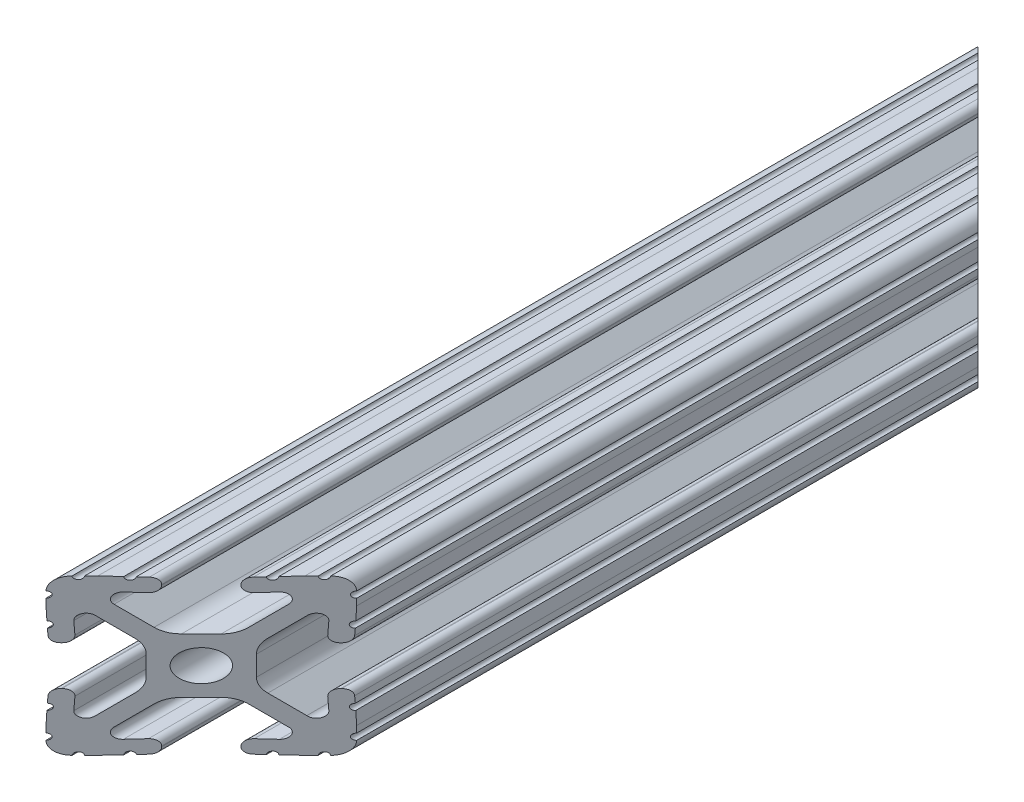
SolidWorks part; units mm, degrees
ref_plane "Front" through (0, 0, 0) normal (0, 0, 1) x (1, 0, 0)
ref_plane "Top" through (0, 0, 0) normal (0, 1, 0) x (1, 0, 0)
ref_plane "Right" through (0, 0, 0) normal (1, 0, 0) x (0, 0, -1)
ref_plane "Bottom" through (0, 25.4, 0) normal (0, 1, 0) x (-1, 0, 0)
ref_plane "Left" through (25.4, 0, 0) normal (1, 0, 0) x (0, 0, -1)
sketch "Sketch1" plane through (0, 0, 0) normal (0, 0, 1) x (1, 0, 0)
  line L0 (25.4334, 2.1492) -> (25.4334, 2.1323)
  line L1 (23.3169, 0.0156) -> (23.3, 0.0156)
  line L2 (22.284, 0.0156) -> (21.2003, 0.0156)
  line L3 (21.2003, 0.0156) -> (19.0664, 0.0901)
  line L4 (6.4007, 0.0901) -> (4.2668, 0.0156)
  line L5 (4.2668, 0.0156) -> (3.1831, 0.0156)
  line L6 (2.1671, 0.0156) -> (2.1502, 0.0156)
  line L7 (0.0335, 2.1323) -> (0.0335, 2.1492)
  line L8 (0.0335, 3.1652) -> (0.0335, 4.249)
  line L9 (0.0335, 4.249) -> (0.1081, 6.3829)
  line L10 (0.108, 19.0484) -> (0.0335, 21.1824)
  line L11 (0.0335, 21.1824) -> (0.0335, 22.2661)
  line L12 (0.0335, 23.2821) -> (0.0335, 23.299)
  line L13 (2.1501, 25.4157) -> (2.1671, 25.4156)
  line L14 (3.1831, 25.4156) -> (4.2668, 25.4156)
  line L15 (4.2668, 25.4156) -> (6.4007, 25.3411)
  line L16 (19.0663, 25.3411) -> (21.2003, 25.4156)
  line L17 (21.2003, 25.4156) -> (22.284, 25.4156)
  line L18 (23.2999, 25.4156) -> (23.3169, 25.4156)
  line L19 (25.4336, 23.299) -> (25.4336, 23.2821)
  line L20 (25.4336, 22.2661) -> (25.4336, 21.1824)
  line L21 (25.4336, 21.1824) -> (25.3591, 19.0485)
  line L22 (25.3589, 6.3829) -> (25.4334, 4.249)
  line L23 (25.4334, 4.249) -> (25.4334, 3.1652)
  line L24 (12.7336, 17.2115) -> (11.1094, 17.2115)
  line L25 (7.6974, 19.3084) -> (8.8644, 18.1414)
  line L26 (8.2292, 12.7156) -> (8.2292, 14.3482)
  line L27 (12.7336, 17.2115) -> (14.3575, 17.2115)
  line L28 (17.2378, 12.7156) -> (17.2378, 14.3484)
  line L29 (17.2378, 12.7156) -> (17.2378, 11.0831)
  line L30 (8.2292, 12.7156) -> (8.2292, 11.0831)
  line L31 (16.6026, 18.1414) -> (19.7969, 21.3357)
  line L32 (18.1678, 8.8381) -> (21.3535, 5.6523)
  line L33 (5.6701, 4.0957) -> (8.8643, 7.2899)
  line L34 (12.7336, 8.2198) -> (11.1094, 8.2198)
  line L35 (12.7336, 8.2198) -> (14.3574, 8.2198)
  line L36 (19.7967, 4.0956) -> (16.6025, 7.2899)
  line L37 (7.2993, 16.5932) -> (4.0415, 19.8511)
  line L38 (7.2993, 8.838) -> (4.0415, 5.5802)
  line L39 (7.6974, 19.3084) -> (5.5981, 21.4076)
  line L40 (7.4161, 25.3057) -> (8.4818, 25.25)
  line L41 (8.4086, 23.0512) -> (6.352, 23.1414)
  line L42 (9.4951, 24.1004) -> (9.4951, 24.2008)
  line L43 (0.1992, 16.9673) -> (0.1435, 18.0331)
  line L44 (1.3488, 15.9541) -> (1.2484, 15.9541)
  line L45 (2.398, 17.0406) -> (2.3077, 19.0972)
  line L46 (0.1435, 7.3983) -> (0.1992, 8.464)
  line L47 (1.2484, 9.4772) -> (1.3488, 9.4773)
  line L48 (2.398, 8.3907) -> (2.3077, 6.3341)
  line L49 (8.4819, 0.1813) -> (7.4161, 0.1256)
  line L50 (9.4951, 1.3309) -> (9.4951, 1.2305)
  line L51 (8.4086, 2.3801) -> (6.352, 2.2898)
  line L52 (18.0509, 0.1256) -> (16.9852, 0.1813)
  line L53 (17.0585, 2.3801) -> (19.1151, 2.2898)
  line L54 (25.2677, 8.464) -> (25.3235, 7.3983)
  line L55 (24.1183, 9.4772) -> (24.2187, 9.4773)
  line L56 (23.0691, 8.3907) -> (23.1594, 6.3341)
  line L57 (25.3235, 18.0331) -> (25.2678, 16.9674)
  line L58 (23.069, 17.0407) -> (23.1593, 19.0973)
  line L59 (16.984, 25.25) -> (18.0509, 25.3057)
  line L60 (15.9709, 24.1004) -> (15.9709, 24.2008)
  line L61 (17.0573, 23.0512) -> (19.1151, 23.1414)
  line L62 (15.972, 1.3309) -> (15.972, 1.2305)
  line L63 (18.1678, 16.5934) -> (21.4254, 19.8511)
  arc A0 (25.4334, 3.1652) -> (25.4334, 2.1492) centre (25.4334, 2.6572) ccw
  arc A1 (23.3169, 0.0156) -> (25.4334, 2.1323) centre (23.3168, 2.1323) ccw
  arc A2 (23.3, 0.0156) -> (22.284, 0.0156) centre (22.792, 0.0105) ccw
  arc A3 (19.0664, 0.0901) -> (18.0509, 0.1256) centre (18.5588, 0.1118) ccw
  arc A4 (7.4161, 0.1256) -> (6.4007, 0.0901) centre (6.9084, 0.1079) ccw
  arc A5 (3.1831, 0.0156) -> (2.1671, 0.0156) centre (2.6751, 0.012) ccw
  arc A6 (0.0335, 2.1323) -> (2.1502, 0.0156) centre (2.1502, 2.1323) ccw
  arc A7 (0.0335, 2.1492) -> (0.0335, 3.1652) centre (0.0335, 2.6572) ccw
  arc A8 (0.1081, 6.3829) -> (0.1435, 7.3983) centre (0.1291, 6.8905) ccw
  arc A9 (0.1435, 18.0331) -> (0.108, 19.0484) centre (0.1258, 18.5408) ccw
  arc A10 (0.0335, 22.2661) -> (0.0335, 23.2821) centre (0.0371, 22.7741) ccw
  arc A11 (2.1501, 25.4157) -> (0.0335, 23.299) centre (2.1502, 23.299) ccw
  arc A12 (2.1671, 25.4156) -> (3.1831, 25.4156) centre (2.6751, 25.412) ccw
  arc A13 (6.4007, 25.3411) -> (7.4161, 25.3057) centre (6.9085, 25.3266) ccw
  arc A14 (18.0509, 25.3057) -> (19.0663, 25.3411) centre (18.5586, 25.3234) ccw
  arc A15 (22.284, 25.4156) -> (23.2999, 25.4156) centre (22.792, 25.412) ccw
  arc A16 (25.4336, 23.299) -> (23.3169, 25.4156) centre (23.3169, 23.299) ccw
  arc A17 (25.4336, 23.2821) -> (25.4336, 22.2661) centre (25.4336, 22.7741) ccw
  arc A18 (25.3591, 19.0485) -> (25.3235, 18.0331) centre (25.3338, 18.5411) ccw
  arc A19 (25.3235, 7.3983) -> (25.3589, 6.3829) centre (25.3412, 6.8906) ccw
  circle A20 centre (12.7336, 12.7156) radius 2.5527
  arc A21 (8.8644, 18.1414) -> (11.1094, 17.2115) centre (11.1094, 20.3865) ccw
  arc A22 (8.2292, 14.3482) -> (7.2993, 16.5932) centre (5.0542, 14.3482) ccw
  arc A23 (14.3575, 17.2115) -> (16.6026, 18.1414) centre (14.3575, 20.3865) ccw
  arc A24 (18.1678, 16.5934) -> (17.2378, 14.3484) centre (20.4128, 14.3484) ccw
  arc A25 (17.2378, 11.0831) -> (18.1678, 8.8381) centre (20.4128, 11.0831) ccw
  arc A26 (7.2993, 8.838) -> (8.2292, 11.0831) centre (5.0542, 11.0831) ccw
  arc A27 (11.1094, 8.2198) -> (8.8643, 7.2899) centre (11.1094, 5.0448) ccw
  arc A28 (16.6025, 7.2899) -> (14.3574, 8.2198) centre (14.3574, 5.0448) ccw
  arc A29 (4.0415, 19.8511) -> (2.3077, 19.0972) centre (3.3231, 19.1327) ccw
  arc A30 (2.3077, 6.3341) -> (4.0415, 5.5802) centre (3.3231, 6.2986) ccw
  arc A31 (5.6701, 4.0957) -> (6.352, 2.2898) centre (6.308, 3.3049) ccw
  arc A32 (19.1151, 2.2898) -> (19.7967, 4.0956) centre (19.1587, 3.3049) ccw
  arc A33 (21.3535, 5.6523) -> (23.1594, 6.3341) centre (22.1443, 6.2902) ccw
  arc A34 (23.1593, 19.0973) -> (21.4254, 19.8511) centre (22.1439, 19.1327) ccw
  arc A35 (19.7969, 21.3357) -> (19.1151, 23.1414) centre (19.1588, 22.1264) ccw
  arc A36 (6.352, 23.1414) -> (5.5981, 21.4076) centre (6.3165, 22.1261) ccw
  arc A37 (9.4951, 24.2008) -> (8.4818, 25.25) centre (8.4452, 24.2008) ccw
  arc A38 (8.4086, 23.0512) -> (9.4951, 24.1004) centre (8.4452, 24.1004) ccw
  arc A39 (0.1992, 16.9673) -> (1.2484, 15.9541) centre (1.2484, 17.004) ccw
  arc A40 (1.3488, 15.9541) -> (2.398, 17.0406) centre (1.3488, 17.004) ccw
  arc A41 (1.2484, 9.4772) -> (0.1992, 8.464) centre (1.2484, 8.4273) ccw
  arc A42 (2.398, 8.3907) -> (1.3488, 9.4773) centre (1.3488, 8.4274) ccw
  arc A43 (8.4819, 0.1813) -> (9.4951, 1.2305) centre (8.4452, 1.2305) ccw
  arc A44 (9.4951, 1.3309) -> (8.4086, 2.3801) centre (8.4452, 1.3309) ccw
  arc A45 (15.972, 1.2305) -> (16.9852, 0.1813) centre (17.0219, 1.2305) ccw
  arc A46 (17.0585, 2.3801) -> (15.972, 1.3309) centre (17.0219, 1.3309) ccw
  arc A47 (25.2677, 8.464) -> (24.2187, 9.4773) centre (24.2185, 8.4274) ccw
  arc A48 (24.1183, 9.4772) -> (23.0691, 8.3907) centre (24.1183, 8.4274) ccw
  arc A49 (24.2186, 15.9542) -> (25.2678, 16.9674) centre (24.2186, 17.004) ccw
  arc A50 (23.069, 17.0407) -> (24.2186, 15.9542) centre (24.118, 16.9992) ccw
  arc A51 (16.984, 25.25) -> (15.9709, 24.2008) centre (17.0207, 24.2008) ccw
  arc A52 (15.9709, 24.1004) -> (17.0573, 23.0512) centre (17.0207, 24.1004) ccw
extrude "Extrude1" add sketch "Sketch1" against normal blind 1219.2
ref_axis "Axis1" through (12.7336, 12.7156, -10.1764) along (0, 0, -1)
sketch "Sketch2" plane through (0, 0, 0) normal (0, 1, 0) x (1, 0, 0)
  line L0 (0, 0) -> (25.4336, 25.4224)
  line L1 (25.4336, 1219.2) -> (25.4336, 0) construction
  line L2 (25.4336, 25.4224) -> (25.4336, 126.9887)
  line L3 (25.4336, 126.9887) -> (0.0335, 152.4)
  line L4 (0.0335, 1219.2) -> (0.0335, 0) construction
  line L5 (0.0335, 152.4) -> (0, 0)
  dimension "D1" = 152.4
  dimension "D2" = 45
  dimension "D3" = 45
extrude "Cut-Extrude2" cut sketch "Sketch2" along normal through all flip side to cut
